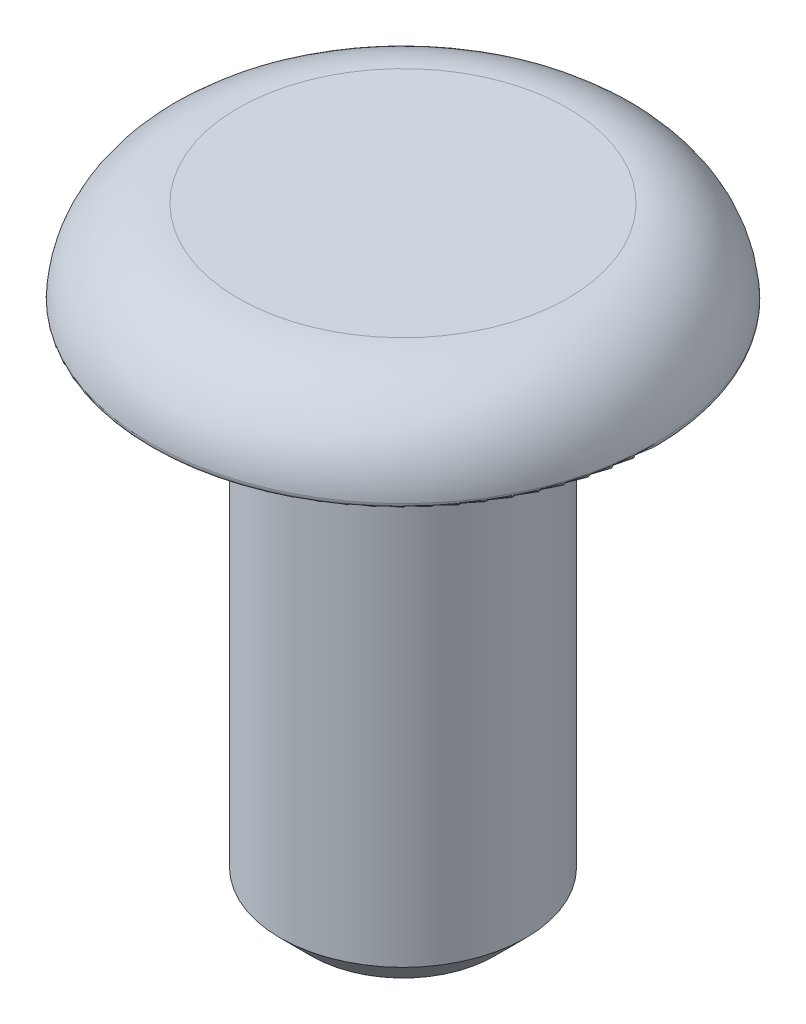
SolidWorks part; units mm, degrees
ref_plane "Front Plane" through (0, 0, 0) normal (0, 0, 1) x (1, 0, 0)
ref_plane "Top Plane" through (0, 0, 0) normal (0, 1, 0) x (1, 0, 0)
ref_plane "Right Plane" through (0, 0, 0) normal (1, 0, 0) x (0, 0, -1)
sketch "Sketch1" plane through (0, 0, 0) normal (0, 1, 0) x (1, 0, 0)
  circle A0 centre (0, 0) radius 1.1112
  dimension "D1" = 2.2225
extrude "Boss-Extrude1" add sketch "Sketch1" along normal blind 4.699
sketch "Sketch2" plane through (0, 4.699, 0) normal (0, 1, 0) x (1, 0, 0)
  circle A1 centre (0, 0) radius 2.286
  circle A2 centre (0, 0) radius 1.1112 construction
  dimension "D1" = 4.572
extrude "Boss-Extrude2" add sketch "Sketch2" along normal blind 0.7937
fillet "Fillet1" radius 0.7937 1 edges at (0, 5.4928, 2.286)
fillet "Fillet2" radius 0.0496 1 edges at (0, 4.699, 2.286)
chamfer "Chamfer1" distance 0.2858 angle 45 1 edges at (0, 0, 1.1112)
